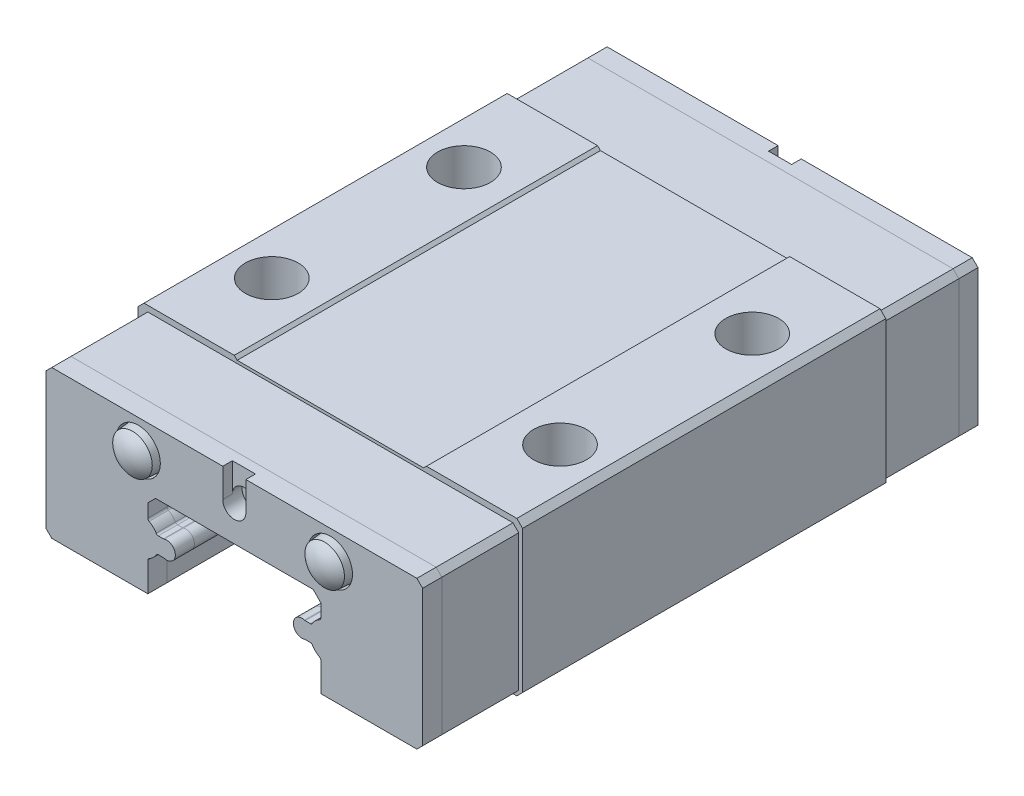
SolidWorks part; units mm, degrees
ref_plane "Front plane" through (0, 0, 0) normal (0, 0, 1) x (1, 0, 0)
ref_plane "Top plane" through (0, 0, 0) normal (0, 1, 0) x (1, 0, 0)
ref_plane "Right Plane" through (0, 0, 0) normal (1, 0, 0) x (0, 0, -1)
sketch "Sketch1" plane through (0, 0, 0) normal (0, 0, 1) x (1, 0, 0)
  line L0 (4.5, 0) -> (9.7, 0)
  line L1 (-9.7, 8) -> (-5, 8)
  line L2 (-10, 7.7) -> (-10, 0.3)
  line L3 (-9.7, 0) -> (-4.5, 0)
  line L4 (10, 7.7) -> (10, 0.3)
  line L5 (-10, 7.7) -> (-9.7, 8)
  line L6 (9.7, 8) -> (10, 7.7)
  line L8 (4.5, 0) -> (4.5, 1.508)
  line L9 (4.1, 4.5) -> (-4.1, 4.5)
  line L11 (-5, 8) -> (-4.85, 7.85)
  line L12 (-4.85, 7.85) -> (4.85, 7.85)
  line L13 (4.85, 7.85) -> (5, 8)
  line L14 (5, 8) -> (9.7, 8)
  line L15 (-10, 0.3) -> (-9.7, 0)
  line L16 (9.7, 0) -> (10, 0.3)
  line L17 (4.1, 4.5) -> (4.5, 4.1)
  line L18 (4.5, 3.412) -> (4.5, 4.1)
  line L19 (3.6884, 2.885) -> (3.9535, 2.885)
  line L21 (3.6884, 2.035) -> (3.9535, 2.035)
  line L23 (0, 4.5) -> (0, 0) construction
  line L24 (-4.5, 0) -> (-4.5, 1.508)
  line L25 (-3.6884, 2.035) -> (-3.9535, 2.035)
  line L26 (-3.6884, 2.885) -> (-3.9535, 2.885)
  line L27 (-4.5, 3.412) -> (-4.5, 4.1)
  line L28 (-4.1, 4.5) -> (-4.5, 4.1)
  arc A0 (4.065, 1.9718) -> (4.4314, 1.6226) centre (4.88, 2.46) ccw
  arc A1 (3.6507, 2.8906) -> (3.6507, 2.0294) centre (3.52, 2.46) ccw
  arc A2 (4.4314, 3.2974) -> (4.065, 2.9482) centre (4.88, 2.46) ccw
  arc A3 (4.5, 1.508) -> (4.4314, 1.6226) centre (4.37, 1.508) ccw
  arc A4 (3.9535, 2.035) -> (4.065, 1.9718) centre (3.9535, 1.905) cw
  arc A5 (3.6507, 2.0294) -> (3.6884, 2.035) centre (3.6884, 1.905) cw
  arc A6 (3.6884, 2.885) -> (3.6507, 2.8906) centre (3.6884, 3.015) cw
  arc A7 (3.9535, 2.885) -> (4.065, 2.9482) centre (3.9535, 3.015) ccw
  arc A8 (4.5, 3.412) -> (4.4314, 3.2974) centre (4.37, 3.412) cw
  arc A9 (-4.5, 1.508) -> (-4.4314, 1.6226) centre (-4.37, 1.508) cw
  arc A10 (-4.065, 1.9718) -> (-4.4314, 1.6226) centre (-4.88, 2.46) cw
  arc A11 (-3.9535, 2.035) -> (-4.065, 1.9718) centre (-3.9535, 1.905) ccw
  arc A12 (-3.6507, 2.0294) -> (-3.6884, 2.035) centre (-3.6884, 1.905) ccw
  arc A13 (-3.6884, 2.885) -> (-3.6507, 2.8906) centre (-3.6884, 3.015) ccw
  arc A14 (-3.6507, 2.8906) -> (-3.6507, 2.0294) centre (-3.52, 2.46) cw
  arc A15 (-3.9535, 2.885) -> (-4.065, 2.9482) centre (-3.9535, 3.015) cw
  arc A16 (-4.4314, 3.2974) -> (-4.065, 2.9482) centre (-4.88, 2.46) cw
  arc A17 (-4.5, 3.412) -> (-4.4314, 3.2974) centre (-4.37, 3.412) ccw
  point P2 (0, 7.85)
  point P34 (4.0304, 2.035)
  point P37 (3.6679, 2.035)
  point P40 (3.6679, 2.885)
  point P43 (4.0304, 2.885)
  point P46 (4.5, 3.3307)
  dimension "D8" = 0.95
  dimension "D10" = 0.45
  dimension "D14" = 0.13
  dimension "D1" = 8
  dimension "D2" = 0.4
  dimension "D3" = 20
  dimension "D4" = 4.5
  dimension "D5" = 0.3
  dimension "D6" = 10
  dimension "D7" = 0.15
  dimension "D9" = 0.38
  dimension "D11" = 1.36
  dimension "D12" = 0.85
  dimension "D13" = 2.04
  dimension "D15" = 9
extrude "Boss-Extrude1" add sketch "Sketch1" along normal mid plane 18.9
sketch "Sketch3" plane through (0, 0, 9.45) normal (0, 0, 1) x (1, 0, 0)
  line L0 (9.5, 0) -> (9.8, 0.3)
  line L1 (9.8, 0.3) -> (9.8, 7.4)
  line L2 (9.5, 7.7) -> (-9.5, 7.7)
  line L3 (-9.5, 7.7) -> (-9.8, 7.4)
  line L4 (-9.8, 7.4) -> (-9.8, 0.3)
  line L5 (-9.8, 0.3) -> (-9.5, 0)
  line L6 (9.5, 7.7) -> (9.8, 7.4)
  line L7 (9.7, 0) -> (10, 0.3) construction
  line L8 (-10, 0.3) -> (-9.7, 0) construction
  line L9 (9.7, 8) -> (5, 8) construction
  line L24 (-9.7, 8) -> (-10, 7.7)
  line L25 (-10, 7.7) -> (-10, 0.3)
  line L26 (-10, 0.3) -> (-9.7, 0)
  line L27 (-9.7, 0) -> (-4.5, 0)
  line L28 (-4.5, 0) -> (-4.5, 1.508)
  line L29 (-3.9535, 2.035) -> (-3.6884, 2.035)
  line L30 (-3.6884, 2.885) -> (-3.9535, 2.885)
  line L31 (-4.5, 3.412) -> (-4.5, 4.1)
  line L32 (-4.5, 4.1) -> (-4.1, 4.5)
  line L33 (-4.1, 4.5) -> (4.1, 4.5)
  line L34 (4.1, 4.5) -> (4.5, 4.1)
  line L35 (4.5, 4.1) -> (4.5, 3.412)
  line L36 (3.9535, 2.885) -> (3.6884, 2.885)
  line L37 (3.6884, 2.035) -> (3.9535, 2.035)
  line L38 (4.5, 1.508) -> (4.5, 0)
  line L39 (4.5, 0) -> (9.7, 0)
  line L40 (9.7, 0) -> (10, 0.3)
  line L41 (10, 0.3) -> (10, 7.7)
  line L42 (10, 7.7) -> (9.7, 8)
  line L43 (9.7, 8) -> (5, 8)
  line L44 (5, 8) -> (4.85, 7.85)
  line L45 (4.85, 7.85) -> (-4.85, 7.85)
  line L46 (-4.85, 7.85) -> (-5, 8)
  line L47 (-5, 8) -> (-9.7, 8)
  line L51 (-9.5, 0) -> (-4.5, 0)
  line L52 (-4.5, 0) -> (-4.5, 1.508)
  line L53 (-3.9535, 2.035) -> (-3.6884, 2.035)
  line L54 (-3.6884, 2.885) -> (-3.9535, 2.885)
  line L55 (-4.5, 3.412) -> (-4.5, 4.1)
  line L56 (-4.5, 4.1) -> (-4.1, 4.5)
  line L57 (-4.1, 4.5) -> (4.1, 4.5)
  line L58 (4.1, 4.5) -> (4.5, 4.1)
  line L59 (4.5, 4.1) -> (4.5, 3.412)
  line L60 (3.9535, 2.885) -> (3.6884, 2.885)
  line L61 (3.6884, 2.035) -> (3.9535, 2.035)
  line L62 (4.5, 1.508) -> (4.5, 0)
  line L63 (4.5, 0) -> (9.5, 0)
  arc A18 (-4.4314, 1.6226) -> (-4.5, 1.508) centre (-4.37, 1.508) ccw
  arc A19 (-4.4314, 1.6226) -> (-4.065, 1.9718) centre (-4.88, 2.46) ccw
  arc A20 (-3.9535, 2.035) -> (-4.065, 1.9718) centre (-3.9535, 1.905) ccw
  arc A21 (-3.6507, 2.0294) -> (-3.6884, 2.035) centre (-3.6884, 1.905) ccw
  arc A22 (-3.6507, 2.0294) -> (-3.6507, 2.8906) centre (-3.52, 2.46) ccw
  arc A23 (-3.6884, 2.885) -> (-3.6507, 2.8906) centre (-3.6884, 3.015) ccw
  arc A24 (-4.065, 2.9482) -> (-3.9535, 2.885) centre (-3.9535, 3.015) ccw
  arc A25 (-4.065, 2.9482) -> (-4.4314, 3.2974) centre (-4.88, 2.46) ccw
  arc A26 (-4.5, 3.412) -> (-4.4314, 3.2974) centre (-4.37, 3.412) ccw
  arc A27 (4.4314, 3.2974) -> (4.5, 3.412) centre (4.37, 3.412) ccw
  arc A28 (4.4314, 3.2974) -> (4.065, 2.9482) centre (4.88, 2.46) ccw
  arc A29 (3.9535, 2.885) -> (4.065, 2.9482) centre (3.9535, 3.015) ccw
  arc A30 (3.6507, 2.8906) -> (3.6884, 2.885) centre (3.6884, 3.015) ccw
  arc A31 (3.6507, 2.8906) -> (3.6507, 2.0294) centre (3.52, 2.46) ccw
  arc A32 (3.6884, 2.035) -> (3.6507, 2.0294) centre (3.6884, 1.905) ccw
  arc A33 (4.065, 1.9718) -> (3.9535, 2.035) centre (3.9535, 1.905) ccw
  arc A34 (4.065, 1.9718) -> (4.4314, 1.6226) centre (4.88, 2.46) ccw
  arc A35 (4.5, 1.508) -> (4.4314, 1.6226) centre (4.37, 1.508) ccw
  arc A36 (-4.4314, 1.6226) -> (-4.5, 1.508) centre (-4.37, 1.508) ccw
  arc A37 (-4.4314, 1.6226) -> (-4.065, 1.9718) centre (-4.88, 2.46) ccw
  arc A38 (-3.9535, 2.035) -> (-4.065, 1.9718) centre (-3.9535, 1.905) ccw
  arc A39 (-3.6507, 2.0294) -> (-3.6884, 2.035) centre (-3.6884, 1.905) ccw
  arc A40 (-3.6507, 2.0294) -> (-3.6507, 2.8906) centre (-3.52, 2.46) ccw
  arc A41 (-3.6884, 2.885) -> (-3.6507, 2.8906) centre (-3.6884, 3.015) ccw
  arc A42 (-4.065, 2.9482) -> (-3.9535, 2.885) centre (-3.9535, 3.015) ccw
  arc A43 (-4.065, 2.9482) -> (-4.4314, 3.2974) centre (-4.88, 2.46) ccw
  arc A44 (-4.5, 3.412) -> (-4.4314, 3.2974) centre (-4.37, 3.412) ccw
  arc A45 (4.4314, 3.2974) -> (4.5, 3.412) centre (4.37, 3.412) ccw
  arc A46 (4.4314, 3.2974) -> (4.065, 2.9482) centre (4.88, 2.46) ccw
  arc A47 (3.9535, 2.885) -> (4.065, 2.9482) centre (3.9535, 3.015) ccw
  arc A48 (3.6507, 2.8906) -> (3.6884, 2.885) centre (3.6884, 3.015) ccw
  arc A49 (3.6507, 2.8906) -> (3.6507, 2.0294) centre (3.52, 2.46) ccw
  arc A50 (3.6884, 2.035) -> (3.6507, 2.0294) centre (3.6884, 1.905) ccw
  arc A51 (4.065, 1.9718) -> (3.9535, 2.035) centre (3.9535, 1.905) ccw
  arc A52 (4.065, 1.9718) -> (4.4314, 1.6226) centre (4.88, 2.46) ccw
  arc A53 (4.5, 1.508) -> (4.4314, 1.6226) centre (4.37, 1.508) ccw
  dimension "D2" = 19.6
  dimension "D3" = 0.3
  dimension "D1" = 0
extrude "Boss-Extrude2" add sketch "Sketch3" along normal blind 4 separate body
sketch "Sketch4" plane through (0, 0, 13.45) normal (0, 0, 1) x (1, 0, 0)
  line L20 (-4.5, 0) -> (-4.5, 1.508)
  line L21 (-3.9535, 2.035) -> (-3.6884, 2.035)
  line L22 (-3.6884, 2.885) -> (-3.9535, 2.885)
  line L23 (-4.5, 3.412) -> (-4.5, 4.1)
  line L24 (-4.5, 4.1) -> (-4.1, 4.5)
  line L25 (-4.1, 4.5) -> (4.1, 4.5)
  line L26 (4.1, 4.5) -> (4.5, 4.1)
  line L27 (4.5, 4.1) -> (4.5, 3.412)
  line L28 (3.9535, 2.885) -> (3.6884, 2.885)
  line L29 (3.6884, 2.035) -> (3.9535, 2.035)
  line L30 (4.5, 1.508) -> (4.5, 0)
  line L31 (4.5, 0) -> (9.5, 0)
  line L32 (9.5, 0) -> (9.8, 0.3)
  line L33 (9.8, 0.3) -> (9.8, 7.4)
  line L34 (9.8, 7.4) -> (9.5, 7.7)
  line L35 (9.5, 7.7) -> (-9.5, 7.7)
  line L36 (-9.5, 7.7) -> (-9.8, 7.4)
  line L37 (-9.8, 7.4) -> (-9.8, 0.3)
  line L38 (-9.8, 0.3) -> (-9.5, 0)
  line L39 (-9.5, 0) -> (-4.5, 0)
  line L40 (-4.5, 0) -> (-4.5, 1.508)
  line L41 (-3.9535, 2.035) -> (-3.6884, 2.035)
  line L42 (-3.6884, 2.885) -> (-3.9535, 2.885)
  line L43 (-4.5, 3.412) -> (-4.5, 4.1)
  line L44 (-4.5, 4.1) -> (-4.1, 4.5)
  line L45 (-4.1, 4.5) -> (4.1, 4.5)
  line L46 (4.1, 4.5) -> (4.5, 4.1)
  line L47 (4.5, 4.1) -> (4.5, 3.412)
  line L48 (3.9535, 2.885) -> (3.6884, 2.885)
  line L49 (3.6884, 2.035) -> (3.9535, 2.035)
  line L50 (4.5, 1.508) -> (4.5, 0)
  line L51 (4.5, 0) -> (9.5, 0)
  line L52 (9.5, 0) -> (9.8, 0.3)
  line L53 (9.8, 0.3) -> (9.8, 7.4)
  line L54 (9.8, 7.4) -> (9.5, 7.7)
  line L55 (9.5, 7.7) -> (-9.5, 7.7)
  line L56 (-9.5, 7.7) -> (-9.8, 7.4)
  line L57 (-9.8, 7.4) -> (-9.8, 0.3)
  line L58 (-9.8, 0.3) -> (-9.5, 0)
  line L59 (-9.5, 0) -> (-4.5, 0)
  arc A18 (-4.4314, 1.6226) -> (-4.5, 1.508) centre (-4.37, 1.508) ccw
  arc A19 (-4.4314, 1.6226) -> (-4.065, 1.9718) centre (-4.88, 2.46) ccw
  arc A20 (-3.9535, 2.035) -> (-4.065, 1.9718) centre (-3.9535, 1.905) ccw
  arc A21 (-3.6507, 2.0294) -> (-3.6884, 2.035) centre (-3.6884, 1.905) ccw
  arc A22 (-3.6507, 2.0294) -> (-3.6507, 2.8906) centre (-3.52, 2.46) ccw
  arc A23 (-3.6884, 2.885) -> (-3.6507, 2.8906) centre (-3.6884, 3.015) ccw
  arc A24 (-4.065, 2.9482) -> (-3.9535, 2.885) centre (-3.9535, 3.015) ccw
  arc A25 (-4.065, 2.9482) -> (-4.4314, 3.2974) centre (-4.88, 2.46) ccw
  arc A26 (-4.5, 3.412) -> (-4.4314, 3.2974) centre (-4.37, 3.412) ccw
  arc A27 (4.4314, 3.2974) -> (4.5, 3.412) centre (4.37, 3.412) ccw
  arc A28 (4.4314, 3.2974) -> (4.065, 2.9482) centre (4.88, 2.46) ccw
  arc A29 (3.9535, 2.885) -> (4.065, 2.9482) centre (3.9535, 3.015) ccw
  arc A30 (3.6507, 2.8906) -> (3.6884, 2.885) centre (3.6884, 3.015) ccw
  arc A31 (3.6507, 2.8906) -> (3.6507, 2.0294) centre (3.52, 2.46) ccw
  arc A32 (3.6884, 2.035) -> (3.6507, 2.0294) centre (3.6884, 1.905) ccw
  arc A33 (4.065, 1.9718) -> (3.9535, 2.035) centre (3.9535, 1.905) ccw
  arc A34 (4.065, 1.9718) -> (4.4314, 1.6226) centre (4.88, 2.46) ccw
  arc A35 (4.5, 1.508) -> (4.4314, 1.6226) centre (4.37, 1.508) ccw
  arc A36 (-4.4314, 1.6226) -> (-4.5, 1.508) centre (-4.37, 1.508) ccw
  arc A37 (-4.4314, 1.6226) -> (-4.065, 1.9718) centre (-4.88, 2.46) ccw
  arc A38 (-3.9535, 2.035) -> (-4.065, 1.9718) centre (-3.9535, 1.905) ccw
  arc A39 (-3.6507, 2.0294) -> (-3.6884, 2.035) centre (-3.6884, 1.905) ccw
  arc A40 (-3.6507, 2.0294) -> (-3.6507, 2.8906) centre (-3.52, 2.46) ccw
  arc A41 (-3.6884, 2.885) -> (-3.6507, 2.8906) centre (-3.6884, 3.015) ccw
  arc A42 (-4.065, 2.9482) -> (-3.9535, 2.885) centre (-3.9535, 3.015) ccw
  arc A43 (-4.065, 2.9482) -> (-4.4314, 3.2974) centre (-4.88, 2.46) ccw
  arc A44 (-4.5, 3.412) -> (-4.4314, 3.2974) centre (-4.37, 3.412) ccw
  arc A45 (4.4314, 3.2974) -> (4.5, 3.412) centre (4.37, 3.412) ccw
  arc A46 (4.4314, 3.2974) -> (4.065, 2.9482) centre (4.88, 2.46) ccw
  arc A47 (3.9535, 2.885) -> (4.065, 2.9482) centre (3.9535, 3.015) ccw
  arc A48 (3.6507, 2.8906) -> (3.6884, 2.885) centre (3.6884, 3.015) ccw
  arc A49 (3.6507, 2.8906) -> (3.6507, 2.0294) centre (3.52, 2.46) ccw
  arc A50 (3.6884, 2.035) -> (3.6507, 2.0294) centre (3.6884, 1.905) ccw
  arc A51 (4.065, 1.9718) -> (3.9535, 2.035) centre (3.9535, 1.905) ccw
  arc A52 (4.065, 1.9718) -> (4.4314, 1.6226) centre (4.88, 2.46) ccw
  arc A53 (4.5, 1.508) -> (4.4314, 1.6226) centre (4.37, 1.508) ccw
  dimension "D1" = 0
extrude "Boss-Extrude3" add sketch "Sketch4" along normal blind 1 separate body
sketch "Sketch5" plane through (0, 0, 14.45) normal (0, 0, 1) x (1, 0, 0)
  line L0 (9.5, 7.7) -> (-9.5, 7.7) construction
  circle A0 centre (0, 6.2) radius 0.6
  dimension "D2" = 1.2
  dimension "D1" = 1.5
extrude "Cut-Extrude2" cut sketch "Sketch5" against normal through all
sketch "Sketch6" plane through (0, 0, 14.45) normal (0, 0, 1) x (1, 0, 0)
  line L0 (9.5, 7.7) -> (-9.5, 7.7) construction
  line L1 (0.6, 6.2) -> (-0.6, 6.2)
  line L2 (0.6, 6.2) -> (0.6, 7.7)
  line L3 (0.6, 7.7) -> (-0.6, 7.7)
  line L4 (-0.6, 6.2) -> (-0.6, 7.7)
  line L5 (0, 4.5) -> (0, 0) construction
  line L6 (-4.1, 4.5) -> (4.1, 4.5) construction
  circle A0 centre (0, 6.2) radius 0.6 construction
  circle A1 centre (-5, 6.2) radius 1.15
  circle A2 centre (5, 6.2) radius 1.15
  dimension "D2" = 2.3
  dimension "D1" = 10
  dimension "D3" = 1.5
extrude "Cut-Extrude3" cut sketch "Sketch6" against normal blind 0.5
ref_plane "Plane1" through (0, 6.2, 0) normal (0, 1, 0) x (1, 0, 0)
sketch "Sketch7" plane through (0, 6.2, 0) normal (0, 1, 0) x (1, 0, 0)
  line L0 (-5, -13.95) -> (-3.9, -13.95)
  line L1 (-3.9, -13.95) -> (-3.97, -14.75)
  line L2 (-5, -13.95) -> (-5, -15.15)
  line L3 (-6.15, -13.95) -> (-3.85, -13.95) construction
  arc A0 (-5, -15.15) -> (-3.97, -14.75) centre (-5, -13.6239) ccw
  dimension "D1" = 1.1
  dimension "D2" = 85
  dimension "D3" = 1.2
  dimension "D4" = 0.8
revolve "Revolve1" add sketch "Sketch7" angle 360 about L2
pattern_linear "LPattern1" count 2 spacing 10 along (1, 0, 0) of bodies 108
mirror "Mirror1" about plane through (0, 0, 0) normal (0, 0, 1) of bodies 104 107 108 109
sketch "Sketch2" plane through (0, 8, 0) normal (0, 1, 0) x (1, 0, 0)
  line L0 (10, -9.45) -> (10, 9.45) construction
  line L1 (-7.5, -5) -> (7.5, -5) construction
  line L2 (-7.5, -5) -> (-7.5, 5) construction
  line L3 (-7.5, 5) -> (7.5, 5) construction
  line L4 (7.5, -5) -> (7.5, 5) construction
  line L5 (-7.5, -5) -> (7.5, 5) construction
  line L6 (-7.5, 5) -> (7.5, -5) construction
  circle A4 centre (-7.5, 5) radius 1.375
  circle A5 centre (7.5, 5) radius 1.375
  circle A6 centre (7.5, -5) radius 1.375
  circle A7 centre (-7.5, -5) radius 1.375
  point P0 (0, 0)
  point P8 (10, 0)
  dimension "D3" = 2.75
  dimension "D1" = 15
  dimension "D2" = 10
extrude "Cut-Extrude1" cut sketch "Sketch2" against normal blind 2.5
